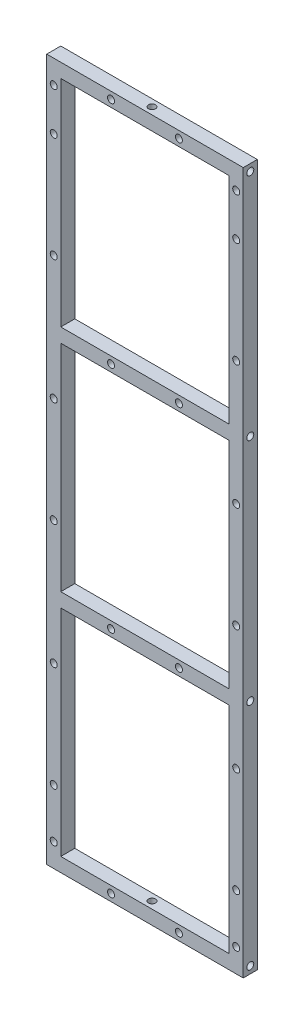
SolidWorks part; units mm, degrees
material "Alumina"
ref_plane "Front Plane" through (0, 0, 0) normal (0, 0, 1) x (1, 0, 0)
ref_plane "Top Plane" through (0, 0, 0) normal (0, 1, 0) x (1, 0, 0)
ref_plane "Right Plane" through (0, 0, 0) normal (1, 0, 0) x (0, 0, -1)
sketch "Sketch1" plane through (0, 0, 0) normal (0, 0, 1) x (1, 0, 0)
  line L0 (36, 144) -> (36, 52)
  line L9 (-42, -150) -> (42, -150)
  line L10 (-42, -150) -> (-42, 150)
  line L11 (-42, 150) -> (42, 150)
  line L12 (42, -150) -> (42, 150)
  line L15 (-36, -144) -> (36, -144)
  line L16 (-36, -144) -> (-36, -52)
  line L17 (-36, 144) -> (36, 144)
  line L21 (-36, 52) -> (36, 52)
  line L23 (-36, 46) -> (36, 46)
  line L25 (-36, -46) -> (36, -46)
  line L27 (-36, -52) -> (36, -52)
  line L33 (36, 46) -> (36, -46)
  line L34 (-36, 52) -> (-36, 144)
  line L35 (-36, -46) -> (-36, 46)
  line L36 (36, -52) -> (36, -144)
  point P0 (0, 0)
  point P4 (0, -46)
  point P6 (0, 0)
  point P20 (0, 0)
  point P21 (0, -150)
  dimension "D1" = 84
  dimension "D2" = 300
  dimension "D3" = 72
  dimension "D4" = 288
  dimension "D5" = 6
  dimension "D6" = 92
  dimension "D7" = 6
  dimension "D8" = 92
  dimension "D9" = 6
  dimension "D10" = 6
  dimension "D11" = 92
extrude "Boss-Extrude1" add sketch "Sketch1" along normal blind 6
sketch "Sketch2" plane through (42, 0, 0) normal (1, 0, 0) x (0, 0, -1)
  line L0 (-6, 150) -> (0, 150) construction
  circle A0 centre (-3, 147) radius 1.5
  circle A1 centre (-3, 49) radius 1.5
  circle A2 centre (-3, -49) radius 1.5
  circle A3 centre (-3, -147) radius 1.5
  dimension "D1" = 3
  dimension "D2" = 4
extrude "Cut-Extrude1" cut sketch "Sketch2" against normal blind 10
mirror "Mirror1" about plane through (0, 0, 0) normal (1, 0, 0) of "Cut-Extrude1"
sketch "Sketch4" plane through (0, 0, 6) normal (0, 0, 1) x (1, 0, 0)
  line L0 (-42, -150) -> (-42, 150) construction
  line L1 (42, -150) -> (42, 150) construction
  line L2 (-42, 150) -> (42, 150) construction
  circle A0 centre (-14.5, 147) radius 1.5
  circle A1 centre (14.5, 147) radius 1.5
  circle A2 centre (14.5, 49) radius 1.5
  circle A3 centre (-14.5, 49) radius 1.5
  circle A4 centre (14.5, -49) radius 1.5
  circle A5 centre (-14.5, -49) radius 1.5
  circle A6 centre (14.5, -147) radius 1.5
  circle A7 centre (-14.5, -147) radius 1.5
  circle A8 centre (-39, 122) radius 1.5
  circle A9 centre (-39, 77) radius 1.5
  circle A10 centre (39, 122) radius 1.5
  circle A11 centre (39, 77) radius 1.5
  circle A12 centre (39, 24) radius 1.5
  circle A13 centre (39, -21) radius 1.5
  circle A14 centre (39, -74) radius 1.5
  circle A15 centre (39, -119) radius 1.5
  circle A16 centre (-39, 24) radius 1.5
  circle A17 centre (-39, -21) radius 1.5
  circle A18 centre (-39, -74) radius 1.5
  circle A19 centre (-39, -119) radius 1.5
  dimension "D1" = 27.5
  dimension "D4" = 45
  dimension "D7" = 2
  dimension "D2" = 27.5
  dimension "D3" = 4
  dimension "D5" = 28
  dimension "D6" = 28
  dimension "D9" = 3
  dimension "D8" = 3
extrude "Cut-Extrude3" cut sketch "Sketch4" against normal blind 10
sketch "Sketch5" plane through (0, 150, 0) normal (0, 1, 0) x (1, 0, 0)
  line L0 (42, -6) -> (-42, -6) construction
  circle A0 centre (0, -3) radius 1.5
  point P5 (0, -6)
  dimension "D1" = 3
extrude "Cut-Extrude4" cut sketch "Sketch5" against normal blind 10
mirror "Mirror2" about plane through (0, 0, 0) normal (0, 1, 0) of "Cut-Extrude4"
sketch "Sketch6" plane through (0, 0, 6) normal (0, 0, 1) x (1, 0, 0)
  line L0 (-42, 150) -> (-42, -150) construction
  line L1 (42, 150) -> (-42, 150) construction
  circle A0 centre (-39, 140) radius 1.5
  dimension "D1" = 3
  dimension "D2" = 3
  dimension "D3" = 10
extrude "Cut-Extrude5" cut sketch "Sketch6" against normal blind 10
pattern_linear "LPattern1" count 2 spacing 78 along (1, 0, 0) count 2 spacing 280 along (0, -1, 0) of "Cut-Extrude5"
